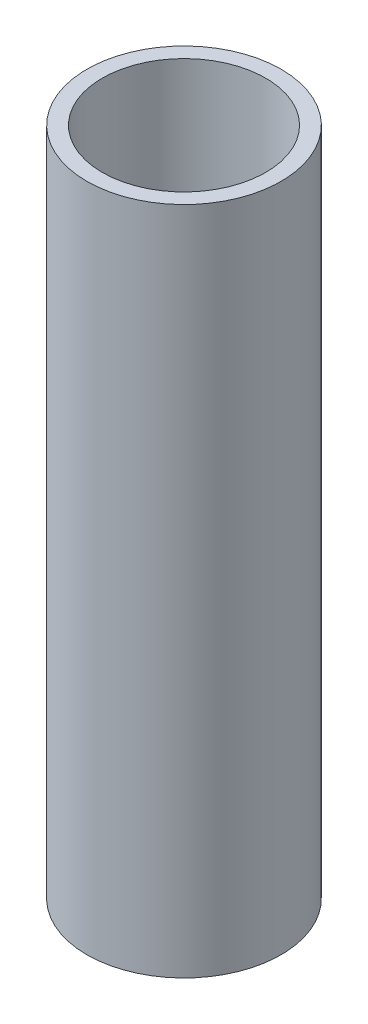
SolidWorks part; units mm, degrees
ref_plane "前视基准面" through (0, 0, 0) normal (0, 0, 1) x (1, 0, 0)
ref_plane "上视基准面" through (0, 0, 0) normal (0, 1, 0) x (1, 0, 0)
ref_plane "右视基准面" through (0, 0, 0) normal (1, 0, 0) x (0, 0, -1)
sketch "草图1" plane through (0, 0, 0) normal (0, 1, 0) x (1, 0, 0)
  circle A1 centre (0, 0) radius 21.75
  dimension "D1" = 43.5
extrude "凸台-拉伸1" add sketch "草图1" along normal blind 150
sketch "草图2" plane through (0, 150, 0) normal (0, 1, 0) x (1, 0, 0)
  circle A0 centre (0, 0) radius 18.3
extrude "切除-拉伸1" cut sketch "草图2" against normal blind 33 contours A0
sketch "草图3" plane through (0, 0, 0) normal (0, -1, 0) x (1, 0, 0)
  circle A0 centre (0, 0) radius 18.3
extrude "切除-拉伸2" cut sketch "草图3" against normal blind 33
